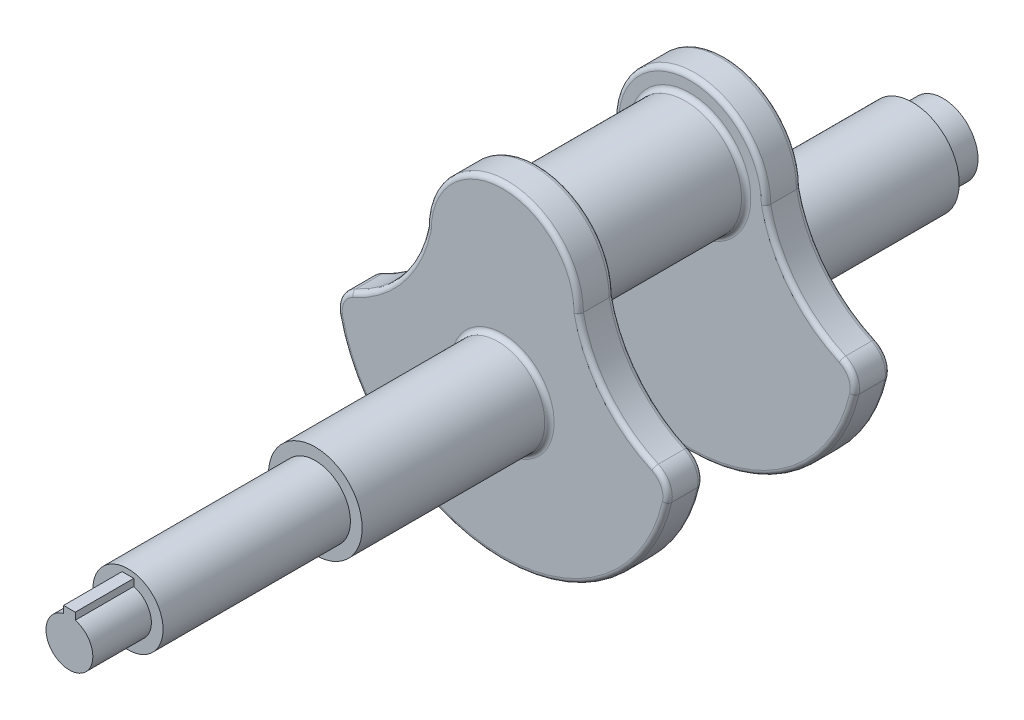
SolidWorks part; units mm, degrees
ref_plane "Front Plane" through (0, 0, 0) normal (0, 0, 1) x (1, 0, 0)
ref_plane "Top Plane" through (0, 0, 0) normal (0, 1, 0) x (1, 0, 0)
ref_plane "Right Plane" through (0, 0, 0) normal (1, 0, 0) x (0, 0, -1)
sketch "Sketch1" plane through (0, 0, 0) normal (0, 0, 1) x (1, 0, 0)
  arc A0 (-32.5, 0) -> (32.5, 0) centre (0, 0) cw
  arc A1 (-32.5, 0) -> (-71.6624, -42.3683) centre (-87.3282, 11.3958) cw
  arc A2 (32.5, 0) -> (71.632, -42.6743) centre (87.3968, 11.0609) ccw
  arc A3 (-71.6624, -42.3683) -> (71.632, -42.6743) centre (0, -35.404) ccw
  point P7 (0, 0)
  dimension "D1" = 32.5
  dimension "D2" = 56
  dimension "D3" = 56
  dimension "D4" = 72
extrude "Boss-Extrude1" add sketch "Sketch1" along normal blind 15
sketch "Sketch2" plane through (0, 0, 0) normal (0, 0, -1) x (-1, 0, 0)
  circle A0 centre (0, 0) radius 24
  dimension "D1" = 48
extrude "Boss-Extrude2" add sketch "Sketch2" along normal blind 65
sketch "Sketch5" plane through (0, 0, -65) normal (0, 0, -1) x (-1, 0, 0)
  circle A1 centre (0, 0) radius 24
  circle A2 centre (0, 0) radius 24
  arc A6 (32.5, 0) -> (-32.5, 0) centre (0, 0) ccw
  arc A7 (-71.632, -42.6743) -> (-32.5, 0) centre (-87.3968, 11.0609) ccw
  arc A8 (-71.632, -42.6743) -> (71.6624, -42.3683) centre (0, -35.404) ccw
  arc A9 (32.5, 0) -> (71.6624, -42.3683) centre (87.3282, 11.3958) ccw
  arc A10 (32.5, 0) -> (-32.5, 0) centre (0, 0) ccw
  arc A11 (-71.632, -42.6743) -> (-32.5, 0) centre (-87.3968, 11.0609) ccw
  arc A12 (-71.632, -42.6743) -> (71.6624, -42.3683) centre (0, -35.404) ccw
  arc A13 (32.5, 0) -> (71.6624, -42.3683) centre (87.3282, 11.3958) ccw
  dimension "D1" = 0
  dimension "D2" = 0
extrude "Boss-Extrude4" add sketch "Sketch5" along normal blind 15 contours A10 A11 A12 A13
sketch "Sketch6" plane through (0, 0, 15) normal (0, 0, 1) x (1, 0, 0)
  circle A0 centre (0, -45) radius 20
  dimension "D1" = 45
  dimension "D2" = 40
extrude "Boss-Extrude5" add sketch "Sketch6" along normal blind 80
sketch "Sketch7" plane through (0, 0, 95) normal (0, 0, 1) x (1, 0, 0)
  circle A0 centre (0, -45) radius 15
  dimension "D1" = 30
extrude "Boss-Extrude6" add sketch "Sketch7" along normal blind 80
sketch "Sketch8" plane through (0, 0, -80) normal (0, 0, -1) x (-1, 0, 0)
  circle A1 centre (0, -45) radius 20
  circle A2 centre (0, -45) radius 20
  dimension "D1" = 0
extrude "Boss-Extrude7" add sketch "Sketch8" along normal blind 80
sketch "Sketch9" plane through (0, 0, -160) normal (0, 0, -1) x (-1, 0, 0)
  circle A0 centre (0, -45) radius 15
  dimension "D1" = 30
extrude "Boss-Extrude8" add sketch "Sketch9" along normal blind 13
sketch "Sketch10" plane through (0, 0, 175) normal (0, 0, 1) x (1, 0, 0)
  circle A0 centre (0, -45) radius 10
  dimension "D1" = 20
extrude "Boss-Extrude9" add sketch "Sketch10" along normal blind 25
sketch "Sketch12" plane through (0, 0, 200) normal (0, 0, 1) x (1, 0, 0)
  line L0 (2.5, -35.3175) -> (-2.5, -35.3175)
  line L1 (-2.5, -35.3175) -> (-2.5, -32.3175)
  line L2 (-2.5, -32.3175) -> (2.5, -32.3175)
  line L3 (2.5, -32.3175) -> (2.5, -35.3175)
  line L4 (0, -48.8055) -> (0, -33.831) construction
  circle A0 centre (0, -45) radius 10 construction
  dimension "D1" = 5
  dimension "D2" = 3
extrude "Boss-Extrude10" add sketch "Sketch12" against normal blind 25
fillet "Fillet1" radius 10 4 edges at (71.632, -42.6743, -72.5) (71.632, -42.6743, 7.5) (-71.6624, -42.3683, 7.5) (-71.6624, -42.3683, -72.5)
fillet "Fillet2" radius 2 28 edges at (-43.7367, -23.7577, -80) (-69.443, -44.4138, -80) (-0.1646, -107.4039, -80) (69.3957, -44.7204, -80) (-43.7367, -23.7577, 0) (-69.443, -44.4138, 0) (-0.1646, -107.4039, 0) (69.3957, -44.7204, 0) (-20, -45, 15) (-20, -45, -80) (43.6601, -23.912, -80) (0, 32.5, -80) (-24, 0, -65) (-24, 0, 0) (43.6601, -23.912, 0) (0, 32.5, 0) (-43.7367, -23.7577, -65) (-69.443, -44.4138, -65) (-0.1646, -107.4039, -65) (69.3957, -44.7204, -65) (-43.7367, -23.7577, 15) (-69.443, -44.4138, 15) (-0.1646, -107.4039, 15) (69.3957, -44.7204, 15) (43.6601, -23.912, -65) (0, 32.5, -65) (43.6601, -23.912, 15) (0, 32.5, 15)
